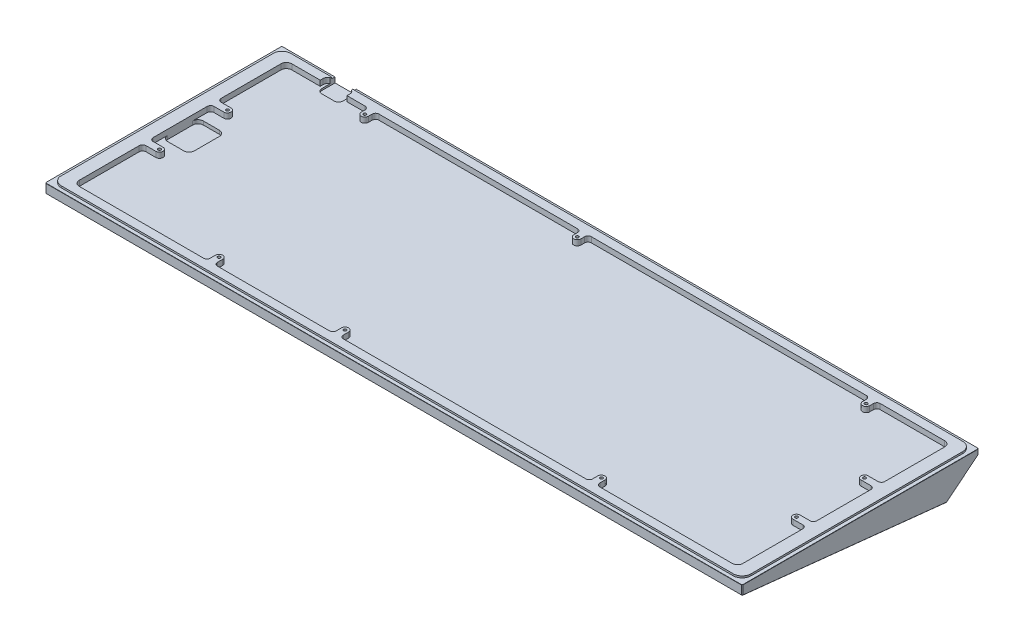
SolidWorks part; units mm, degrees
material "6061-T6 (SS)"
ref_plane "Front Plane" through (0, 0, 0) normal (0, 0, 1) x (1, 0, 0)
ref_plane "Top Plane" through (0, 0, 0) normal (0, 1, 0) x (1, 0, 0)
ref_plane "Right Plane" through (0, 0, 0) normal (1, 0, 0) x (0, 0, -1)
sketch "Sketch1" plane through (0, 0, 0) normal (0, 1, 0) x (1, 0, 0)
  line L1 (0, 0) -> (390.7, 0)
  line L2 (0, 0) -> (0, 132.7)
  line L3 (0, 132.7) -> (390.7, 132.7)
  line L4 (390.7, 0) -> (390.7, 132.7)
  dimension "D1" = 390.7
  dimension "D2" = 132.7
extrude "MainBody" add sketch "Sketch1" along normal blind 18.5
sketch "Sketch2" plane through (0, 18.5, 0) normal (0, 1, 0) x (1, 0, 0)
  line L0 (390.7, 132.7) -> (0, 132.7) construction
  line L1 (2.05, 130.65) -> (388.65, 130.65)
  line L2 (2.05, 130.65) -> (2.05, 2.05)
  line L3 (2.05, 2.05) -> (388.65, 2.05)
  line L4 (388.65, 130.65) -> (388.65, 2.05)
  line L5 (0, 132.7) -> (0, 0) construction
  line L7 (0, 132.7) -> (390.7, 132.7)
  line L8 (0, 132.7) -> (0, 0)
  line L9 (0, 0) -> (390.7, 0)
  line L10 (390.7, 132.7) -> (390.7, 0)
  point P4 (195.35, 130.65)
  point P7 (195.35, 132.7)
  point P8 (2.05, 66.35)
  point P11 (0, 66.35)
  line M5 (0, 132.7) -> (0, 0)
  line M6 (0, 0) -> (390.7, 0)
  line M7 (390.7, 0) -> (390.7, 132.7)
  line M8 (390.7, 132.7) -> (0, 132.7)
  dimension "D1" = 2.05
  dimension "D2" = 2.05
extrude "AligmentLip" cut sketch "Sketch2" against normal blind 1 contours L1 L4 L3 L2 M8 M5 M6 M7
sketch "Sketch3" plane through (0, 0, 0) normal (-1, 0, 0) x (0, 0, 1)
  line L0 (-132.7, 14.5) -> (-114.794, 0)
  line L1 (-132.7, 17.5) -> (-132.7, 0) construction
  line L2 (-132.7, 0) -> (0, 0) construction
  line L3 (-114.794, 0) -> (0, 12.0653)
  line L4 (0, 17.5) -> (0, 0) construction
  line L5 (-132.7, 17.5) -> (0, 17.5) construction
  line L7 (-132.7, 17.5) -> (0, 17.5)
  line L8 (-132.7, 17.5) -> (-132.7, 0)
  line L9 (-132.7, 0) -> (0, 0)
  line L10 (0, 17.5) -> (0, 0)
  line M4 (-132.7, 17.5) -> (-132.7, 0)
  line M5 (-132.7, 0) -> (0, 0)
  line M6 (0, 0) -> (0, 17.5)
  dimension "D1" = 6
  dimension "D2" = 135
  dimension "D3" = 3
extrude "TypingAngle" cut sketch "Sketch3" against normal through all contours L0 M4 M5 | L3 M5 M6
sketch "Sketch4" plane through (0, 18.5, 0) normal (0, 1, 0) x (1, 0, 0)
  line L0 (2.05, 130.65) -> (388.65, 130.65) construction
  line L1 (9.35, 125.9) -> (381.35, 125.9)
  line L2 (9.35, 125.9) -> (9.35, 6.8)
  line L3 (9.35, 6.8) -> (381.35, 6.8)
  line L4 (381.35, 125.9) -> (381.35, 6.8)
  line L5 (2.05, 130.65) -> (2.05, 2.05) construction
  point P4 (195.35, 125.9)
  point P7 (195.35, 130.65)
  point P8 (9.35, 66.35)
  point P11 (2.05, 66.35)
  dimension "D1" = 372
  dimension "D2" = 119.1
extrude "PCBCutout" cut sketch "Sketch4" against normal blind 3
sketch "Sketch13" plane through (0, 15.5, 0) normal (0, 1, 0) x (1, 0, 0)
  line L0 (9.35, 125.9) -> (9.35, 6.8) construction
  line L1 (9.35, 76.35) -> (24.35, 76.35)
  line L2 (9.35, 76.35) -> (9.35, 56.35)
  line L3 (9.35, 56.35) -> (24.35, 56.35)
  line L4 (24.35, 76.35) -> (24.35, 56.35)
  line L5 (2.05, 130.65) -> (2.05, 2.05) construction
  point P6 (9.35, 66.35)
  point P9 (2.05, 66.35)
  dimension "D1" = 15
  dimension "D2" = 20
extrude "Cut-Extrude4" cut sketch "Sketch13" against normal blind 2
fillet "Fillet2" radius 3 8 edges at (381.35, 17, -125.9) (381.35, 17, -6.8) (9.35, 17, -6.8) (9.35, 17, -125.9) (9.35, 14.5, -56.35) (24.35, 14.5, -56.35) (9.35, 14.5, -76.35) (24.35, 14.5, -76.35)
chamfer "Chamfer1" distance 0.5 angle 45 13 edges at (195.35, 12.0653, 0) (390.7, 16, -132.7) (0, 16, -132.7) (0, 7.25, -123.747) (390.7, 7.25, -123.747) (390.7, 6.0327, -57.397) (390.7, 14.7827, 0) (0, 6.0327, -57.397) (0, 14.7827, 0) (0, 17.5, -66.35) (195.35, 17.5, 0) (390.7, 17.5, -66.35) (195.35, 17.5, -132.7)
chamfer "Chamfer2" distance 0.1 angle 45 1 edges at (2.05, 18.5, -66.35)
sketch "Sketch17" plane through (0, 11.9335, -1.2543) normal (0, -0.9945, 0.1045) x (1, 0, 0)
  line L0 (198.25, -60.7388) -> (196.25, -60.7388) construction
  line L1 (198.25, -68.7388) -> (196.25, -68.7388)
  line L2 (198.25, -68.7388) -> (198.25, -52.7388)
  line L3 (198.25, -52.7388) -> (196.25, -52.7388)
  line L4 (196.25, -68.7388) -> (196.25, -52.7388)
  line L5 (202.75, -61.2388) -> (200.75, -61.2388)
  line L6 (202.75, -61.2388) -> (202.75, -48.7388)
  line L7 (202.75, -48.7388) -> (200.75, -48.7388)
  line L8 (200.75, -61.2388) -> (200.75, -48.7388)
  line L9 (193.45, -61.2388) -> (191.45, -61.2388)
  line L10 (193.45, -61.2388) -> (193.45, -53.2388)
  line L11 (193.45, -53.2388) -> (191.45, -53.2388)
  line L12 (191.45, -61.2388) -> (191.45, -53.2388)
  line L13 (189.95, -61.2388) -> (187.95, -61.2388)
  line L14 (189.95, -61.2388) -> (189.95, -53.2388)
  line L15 (189.95, -53.2388) -> (187.95, -53.2388)
  line L16 (187.95, -61.2388) -> (187.95, -53.2388)
  line L17 (186.45, -61.2388) -> (184.45, -61.2388)
  line L18 (186.45, -61.2388) -> (186.45, -53.2388)
  line L19 (186.45, -53.2388) -> (184.45, -53.2388)
  line L20 (184.45, -61.2388) -> (184.45, -53.2388)
  line L25 (202.75, -61.2388) -> (187.95, -61.2388) construction
  line L26 (390.2, -114.1651) -> (0.5, -114.1651) construction
  line L27 (194.25, -64.7388) -> (198.25, -64.7388)
  line L28 (194.25, -62.7388) -> (198.25, -62.7388)
  line L29 (390.7, 1.2612) -> (0, 1.2612) construction
  line L31 (206.25, -53.2388) -> (204.25, -53.2388)
  line L32 (206.25, -53.2388) -> (206.25, -48.7388)
  line L33 (206.25, -48.7388) -> (204.25, -48.7388)
  line L34 (204.25, -53.2388) -> (204.25, -48.7388)
  circle A0 centre (201.75, -63.7388) radius 1
  circle A2 centre (194.25, -63.7388) radius 1
  circle A3 centre (197.25, -67.7388) radius 1
  circle A4 centre (197.25, -53.7388) radius 1
  circle A5 centre (201.75, -60.2388) radius 1
  circle A6 centre (201.75, -49.7388) radius 1
  circle A7 centre (205.25, -52.2388) radius 1
  circle A8 centre (205.25, -49.7388) radius 1
  circle A9 centre (192.45, -60.2388) radius 1
  circle A10 centre (192.45, -54.2388) radius 1
  circle A11 centre (188.95, -60.2388) radius 1
  circle A12 centre (188.95, -54.2388) radius 1
  circle A13 centre (185.45, -60.2388) radius 1
  circle A14 centre (185.45, -54.2388) radius 1
  point P28 (195.35, -61.2388)
  point P29 (201.75, -61.2388)
  point P33 (195.35, -114.1651)
  point P44 (197.25, -68.7388)
  dimension "D12" = 2
  dimension "D13" = 12.5
  dimension "D16" = 2
  dimension "D1" = 16
  dimension "D2" = 2
  dimension "D3" = 0
  dimension "D4" = 2.5
  dimension "D5" = 2.8
  dimension "D6" = 1.5
  dimension "D7" = 1.5
  dimension "D8" = 8
  dimension "D9" = 0.5
  dimension "D10" = 1.5
  dimension "D11" = 2.5
  dimension "D14" = 4.5
  dimension "D15" = 50
  dimension "D17" = 2
  dimension "D18" = 3
  dimension "D19" = 11
extrude "Cut-Extrude5" cut sketch "Sketch17" against normal blind 1 contours A7 | A8 L34 A7 L32 | A8 | A6 | A6 L8 A5 L6 | A5 | A4 | A4 L4 L28 L2 | L28 L4 L27 L2 | A3 L2 L27 L4 | A3 | A2 L27 L4 L28 | A2 | A0 | A9 | A10 L12 A9 L10 | A10 | A12 L16 A11 L14 | A11 | A12 | A14 | A14 L20 A13 L18 | A13
sketch "Sketch18" plane through (0, 0, -132.7) normal (0, 0, -1) x (-1, 0, 0)
  line L1 (-41.8, 18.5) -> (-29.8, 18.5)
  line L2 (-41.8, 18.5) -> (-41.8, 14.5)
  line L3 (-41.8, 14.5) -> (-29.8, 14.5)
  line L4 (-29.8, 18.5) -> (-29.8, 14.5)
  line L5 (0, 17.5) -> (0, 14.7385) construction
  line L6 (-390.2, 14.5) -> (-0.5, 14.5) construction
  line L8 (-2.15, 18.5) -> (-388.65, 18.5) construction
  point P6 (-35.8, 18.5)
  point P11 (0, 0)
  dimension "D1" = 35.8
  dimension "D3" = 12
extrude "Cut-Extrude6" cut sketch "Sketch18" against normal blind 10
sketch "Sketch12" plane through (0, 18.5, 0) normal (0, 1, 0) x (1, 0, 0)
  line L0 (381.35, 125.9) -> (9.35, 125.9) construction
  line L1 (28.3, 125.9) -> (43.3, 125.9)
  line L2 (28.3, 125.9) -> (28.3, 129.85)
  line L3 (28.3, 129.85) -> (43.3, 129.85)
  line L4 (43.3, 125.9) -> (43.3, 129.85)
  line L6 (390.7, 132.7) -> (0, 132.7) construction
  line L7 (41.8, 132.7) -> (29.8, 132.7) construction
  point P6 (35.8, 129.85)
  point P11 (35.8, 132.7)
  dimension "D1" = 15
  dimension "D2" = 2.85
extrude "Cut-Extrude3" cut sketch "Sketch12" against normal up to surface (3 mm away) up to face at (92.04, 15.5, -77.94)
fillet "Fillet1" radius 2.5 4 edges at (43.3, 17, -129.85) (28.3, 17, -129.85) (41.8, 15, -122.7) (29.8, 15, -122.7)
sketch "Sketch19" plane through (0, 15.5, 0) normal (0, 1, 0) x (1, 0, 0)
  line L1 (195.35, 0) -> (195.35, 132.7) construction
  line L6 (378.35, 125.9) -> (43.3, 125.9) construction
  line L7 (55.3, 121.9) -> (59.3, 121.9)
  line L8 (55.3, 121.9) -> (55.3, 125.9)
  line L9 (55.3, 125.9) -> (59.3, 125.9)
  line L10 (59.3, 121.9) -> (59.3, 125.9)
  line L11 (378.35, 125.9) -> (43.3, 125.9) construction
  line L12 (174.4, 121.9) -> (178.4, 121.9)
  line L13 (174.4, 121.9) -> (174.4, 125.9)
  line L14 (174.4, 125.9) -> (178.4, 125.9)
  line L15 (178.4, 121.9) -> (178.4, 125.9)
  line L16 (336.3, 121.9) -> (340.3, 121.9)
  line L17 (336.3, 121.9) -> (336.3, 125.9)
  line L18 (336.3, 125.9) -> (340.3, 125.9)
  line L19 (340.3, 121.9) -> (340.3, 125.9)
  line L20 (381.35, 9.8) -> (381.35, 122.9) construction
  line L21 (373.9, 87.4) -> (381.35, 87.4)
  line L22 (373.9, 87.4) -> (373.9, 83.4)
  line L23 (373.9, 83.4) -> (381.35, 83.4)
  line L24 (381.35, 87.4) -> (381.35, 83.4)
  line L25 (12.35, 6.8) -> (378.35, 6.8) construction
  line L26 (373.9, 49.3) -> (381.35, 49.3)
  line L27 (373.9, 49.3) -> (373.9, 45.3)
  line L28 (373.9, 45.3) -> (381.35, 45.3)
  line L29 (381.35, 49.3) -> (381.35, 45.3)
  line L30 (298.2, 11.6) -> (302.2, 11.6)
  line L31 (298.2, 11.6) -> (298.2, 6.8)
  line L32 (298.2, 6.8) -> (302.2, 6.8)
  line L33 (302.2, 11.6) -> (302.2, 6.8)
  line L34 (12.35, 6.8) -> (378.35, 6.8) construction
  line L35 (158.5, 11.6) -> (154.5, 11.6)
  line L36 (158.5, 11.6) -> (158.5, 6.8)
  line L37 (158.5, 6.8) -> (154.5, 6.8)
  line L38 (154.5, 11.6) -> (154.5, 6.8)
  line L39 (9.35, 59.35) -> (9.35, 9.8) construction
  line L40 (87.9, 11.6) -> (83.9, 11.6)
  line L41 (87.9, 11.6) -> (87.9, 6.8)
  line L42 (87.9, 6.8) -> (83.9, 6.8)
  line L43 (83.9, 11.6) -> (83.9, 6.8)
  line L44 (16.8, 49.3) -> (9.35, 49.3)
  line L45 (16.8, 49.3) -> (16.8, 45.3)
  line L46 (16.8, 45.3) -> (9.35, 45.3)
  line L47 (9.35, 49.3) -> (9.35, 45.3)
  line L48 (9.35, 122.9) -> (9.35, 9.8) construction
  line L49 (16.8, 87.4) -> (9.35, 87.4)
  line L50 (16.8, 87.4) -> (16.8, 83.4)
  line L51 (16.8, 83.4) -> (9.35, 83.4)
  line L52 (9.35, 87.4) -> (9.35, 83.4)
  line L53 (390.2, 132.7) -> (41.8, 132.7) construction
  line L54 (0, 132.2) -> (0, 0.5) construction
  line L55 (0.5, 0) -> (390.2, 0) construction
  circle A0 centre (57.3, 121.9) radius 2
  circle A1 centre (176.4, 121.9) radius 2
  circle A2 centre (338.3, 121.9) radius 2
  circle A3 centre (16.8, 85.4) radius 2
  circle A4 centre (16.8, 47.3) radius 2
  circle A5 centre (85.9, 11.6) radius 2
  circle A6 centre (156.5, 11.6) radius 2
  circle A7 centre (300.2, 11.6) radius 2
  circle A8 centre (373.9, 85.4) radius 2
  circle A9 centre (373.9, 47.3) radius 2
  dimension "D2" = 4
  dimension "D6" = 4
  dimension "D12" = 4
  dimension "D3" = 57.3
  dimension "D4" = 119.1
  dimension "D5" = 161.9
  dimension "D7" = 40.5
  dimension "D8" = 38.1
  dimension "D9" = 36.5
  dimension "D10" = 110.3
  dimension "D11" = 28.6
  dimension "D13" = 70.6
  dimension "D14" = 143.7
  dimension "D15" = 10.8
extrude "Boss-Extrude1" add sketch "Sketch19" along normal up to surface (3 mm away) contours L46 L47 L44 L45 | L51 L52 L49 L50 | A4 | A3 | L10 L9 L8 L7 | A0 | L15 L14 L13 L12 | A1 | L19 L18 L17 L16 | A2 | L21 L24 L23 L22 | A8 | L26 L29 L28 L27 | A9 | L33 L32 L31 L30 | A7 | L36 L37 L38 L35 | A6 | L41 L42 L43 L40 | A5 up to face at (131.54, 18.5, -91.2282)
fillet "Fillet3" radius 1.9 20 edges at (83.9, 17, -6.8) (87.9, 17, -6.8) (158.5, 17, -6.8) (154.5, 17, -6.8) (298.2, 17, -6.8) (302.2, 17, -6.8) (381.35, 17, -45.3) (381.35, 17, -49.3) (381.35, 17, -87.4) (381.35, 17, -83.4) (336.3, 17, -125.9) (340.3, 17, -125.9) (178.4, 17, -125.9) (174.4, 17, -125.9) (59.3, 17, -125.9) (55.3, 17, -125.9) (9.35, 17, -87.4) (9.35, 17, -49.3) (9.35, 17, -45.3) (9.35, 17, -83.4)
sketch "Sketch20" plane through (0, 18.5, 0) normal (0, 1, 0) x (1, 0, 0)
  point P0 (16.8, 47.3)
  point P1 (16.8, 85.4)
  point P3 (85.9, 11.6)
  point P5 (156.5, 11.6)
  point P7 (300.2, 11.6)
  point P9 (373.9, 47.3)
  point P11 (373.9, 85.4)
  point P13 (338.3, 121.9)
  point P15 (176.4, 121.9)
  point P17 (57.3, 121.9)
hole_wizard "M2x0.4 Tapped Hole1" positions "3DSketch3" profile "Sketch22" tap size "M2x0.4" standard "ANSI Metric"
sketch3d "3DSketch3"
  point P0 (57.3, 18.5, -121.9)
  point P3 (176.4, 18.5, -121.9)
  point P6 (16.8, 18.5, -47.3)
  point P9 (16.8, 18.5, -85.4)
  point P12 (85.9, 18.5, -11.6)
  point P15 (156.5, 18.5, -11.6)
  point P18 (300.2, 18.5, -11.6)
  point P21 (373.9, 18.5, -47.3)
  point P24 (373.9, 18.5, -85.4)
  point P27 (338.3, 18.5, -121.9)
sketch "Sketch22" plane through (57.3, 18.5, -121.9) normal (1, 0, 0) x (0, 0, 1)
  line L0 (0, 0) -> (0, 4.4807)
  line L1 (0, 4.4807) -> (0.8, 4)
  line L2 (0.8, 4) -> (0.8, 0)
  line L5 (0.8, 0) -> (0, 0)
  line L10 (0, 4.4807) -> (-0.8, 4) construction
  line L11 (0, -6.35) -> (0, 107.95) construction
  dimension "Tap Drill Dia." = 1.6
  dimension "Tap Drill Depth" = 4
  dimension "Drill Angle" = 118
cosmetic thread "Hole Thread1" parameters "D1"=4, "D2"=2
cosmetic thread "Hole Thread2" parameters "D1"=4, "D2"=2
cosmetic thread "Hole Thread3" parameters "D1"=4, "D2"=2
cosmetic thread "Hole Thread4" parameters "D1"=4, "D2"=2
cosmetic thread "Hole Thread5" parameters "D1"=4, "D2"=2
cosmetic thread "Hole Thread6" parameters "D1"=4, "D2"=2
cosmetic thread "Hole Thread7" parameters "D1"=4, "D2"=2
cosmetic thread "Hole Thread8" parameters "D1"=4, "D2"=2
cosmetic thread "Hole Thread9" parameters "D1"=4, "D2"=2
cosmetic thread "Hole Thread10" parameters "D1"=4, "D2"=2
chamfer "Chamfer3" distance 0.1 angle 45 5 edges at (390.7, 17.5, -66.35) (216, 17.5, -132.7) (15.15, 17.5, -132.7) (195.35, 17.5, 0) (0, 17.5, -66.35)
fillet "Fillet4" radius 5 4 edges at (388.65, 18, -2.05) (388.65, 18, -130.65) (2.05, 17.95, -2.05) (2.05, 17.95, -130.65)
